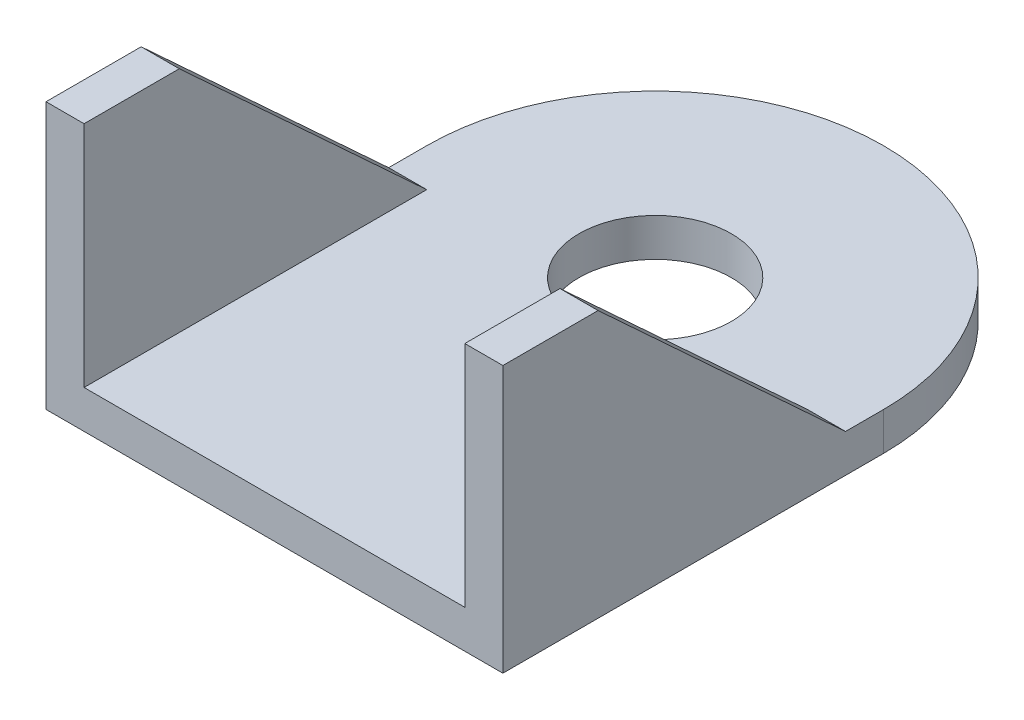
SolidWorks part; units mm, degrees
material "AISI 304"
ref_plane "前视基准面" through (0, 0, 0) normal (0, 0, 1) x (1, 0, 0)
ref_plane "上视基准面" through (0, 0, 0) normal (0, 1, 0) x (1, 0, 0)
ref_plane "右视基准面" through (0, 0, 0) normal (1, 0, 0) x (0, 0, -1)
sketch "草图1" plane through (0, 0, 0) normal (0, 1, 0) x (1, 0, 0)
  line L0 (-12, 0) -> (-12, -20)
  line L1 (-12, -20) -> (12, -20)
  line L2 (12, -20) -> (12, 0)
  circle A0 centre (0, 0) radius 4
  circle A1 centre (0, 0) radius 12
  dimension "D1" = 8
  dimension "D2" = 24
  dimension "D3" = 20
extrude "凸台-拉伸1" add sketch "草图1" along normal blind 2 contours A1 A0 | A1 L0 L1 L2 region at (0, 0, 14.3732) region at (0, 0, -11.6606)
sketch "草图3" plane through (12, 0, 0) normal (1, 0, 0) x (0, 0, -1)
  line L0 (-20, 2) -> (-20, 14)
  line L1 (-20, 14) -> (-15, 14)
  line L2 (-15, 14) -> (-2, 2)
  line L4 (-20, 2) -> (0, 2) construction
  line L5 (-2, 2) -> (-20, 2)
  dimension "D1" = 5
  dimension "D2" = 18
  dimension "D4" = 12
extrude "凸台-拉伸2" add sketch "草图3" against normal blind 2
mirror "镜向1" about plane through (0, 0, 0) normal (1, 0, 0) of "凸台-拉伸2"
ref_plane "基准面1" through (0, 0, 0) normal (0, 0, 1) x (1, 0, 0)
sketch "草图4" [suppressed] plane through (0, 0, 0) normal (0, 0, 1) x (1, 0, 0)
  circle A0 centre (0, 0) radius 41.9162
sketch "草图7" plane through (0, 0, 0) normal (0, -1, 0) x (1, 0, 0)
  circle A0 centre (0, 0) radius 9
split line "分割线1"
sketch "草图8" plane through (0, 0, 0) normal (0, -1, 0) x (1, 0, 0)
  circle A0 centre (0, 0) radius 12
split line "分割线2"
